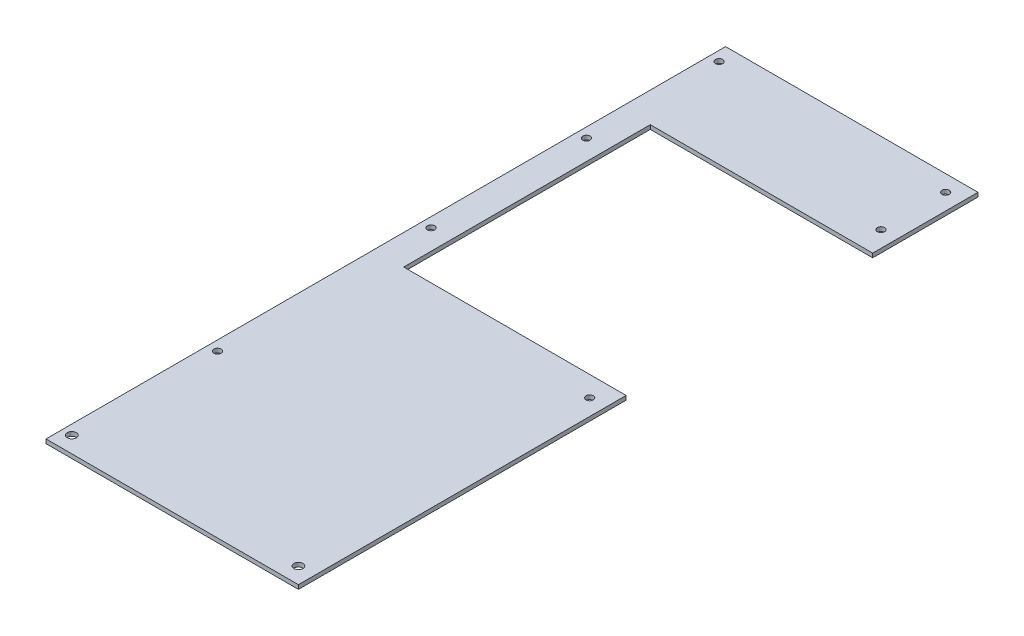
SolidWorks part; units mm, degrees
ref_plane "Front Plane" through (0, 0, 0) normal (1, 0, 0) x (0, 1, 0)
ref_plane "Top Plane" through (0, 0, 0) normal (0, 0, 1) x (0, 1, 0)
ref_plane "Right Plane" through (0, 0, 0) normal (0, 1, 0) x (-1, 0, 0)
sketch "Sketch1" plane through (0, 0, 0) normal (0, 1, 0) x (-1, 0, 0)
  line L0 (187.5, 235) -> (187.5, 275) construction
  line L1 (0, 275) -> (200, 275)
  line L2 (0, 275) -> (0, 525)
  line L3 (0, 525) -> (200, 525)
  line L4 (200, 275) -> (200, 525)
  line L5 (0, 275) -> (200, 525) construction
  line L6 (0, 525) -> (200, 275) construction
  line L7 (200, 275) -> (175, 275)
  line L8 (200, 275) -> (200, 0)
  line L9 (200, 0) -> (175, 0)
  line L10 (175, 275) -> (175, 0)
  line L11 (200, 275) -> (175, 0) construction
  line L12 (200, 0) -> (175, 275) construction
  line L13 (175, 0) -> (0, 0)
  line L14 (175, 0) -> (175, 75)
  line L15 (175, 75) -> (0, 75)
  line L16 (0, 0) -> (0, 75)
  line L17 (175, 0) -> (0, 75) construction
  line L18 (175, 75) -> (0, 0) construction
  line L19 (187.5, 115) -> (187.5, 0) construction
  line L20 (187.5, 512.5) -> (187.5, 235) construction
  circle A0 centre (12.5, 512.5) radius 3.5
  circle A1 centre (12.5, 287.5) radius 2.8
  circle A2 centre (187.5, 512.5) radius 3.5
  circle A3 centre (12.5, 62.5) radius 2.8
  circle A4 centre (12.5, 12.5) radius 2.8
  circle A5 centre (187.5, 12.5) radius 2.8
  circle A7 centre (187.5, 235) radius 2.8
  circle A8 centre (187.5, 115) radius 2.8
  circle A9 centre (187.5, 400) radius 2.8
  point P4 (100, 400)
  point P8 (187.5, 137.5)
  point P12 (87.5, 37.5)
  point P14 (0, 37.5)
  dimension "D7" = 5.6
  dimension "D22" = 7
  dimension "D1" = 25
  dimension "D2" = 250
  dimension "D3" = 200
  dimension "D4" = 200
  dimension "D5" = 200
  dimension "D6" = 75
  dimension "D8" = 12.5
  dimension "D9" = 12.5
  dimension "D10" = 12.5
  dimension "D11" = 12.5
  dimension "D12" = 12.5
  dimension "D13" = 12.5
  dimension "D14" = 12.5
  dimension "D15" = 12.5
  dimension "D16" = 12.5
  dimension "D17" = 12.5
  dimension "D18" = 12.5
  dimension "D19" = 12.5
  dimension "D20" = 40
  dimension "D21" = 40
  dimension "D23" = 125
extrude "Boss-Extrude1" add sketch "Sketch1" along normal blind 3.175 contours L1 L4 L3 L2 A2 A1 A0 | L1 L10 L9 L8 A8 A7 A5 | L16 L13 L10 L15 A4 A3 region at (-100, 0, 399.8819) region at (-187.5, 0, 137.6811) region at (-87.7825, 0, 37.5)
sketch "Sketch2" plane through (0, 3.175, 0) normal (0, 1, 0) x (-1, 0, 0)
  line L0 (175, 275) -> (175, 75) construction
  line L1 (0, 275) -> (175, 275)
  line L2 (0, 275) -> (0, 271.825)
  line L3 (0, 271.825) -> (175, 271.825)
  line L4 (175, 275) -> (175, 271.825)
  line L5 (0, 275) -> (175, 271.825) construction
  line L6 (0, 271.825) -> (175, 275) construction
  line L7 (175, 75) -> (0, 75) construction
  line L8 (175, 271.825) -> (171.825, 271.825)
  line L9 (175, 271.825) -> (175, 75)
  line L10 (175, 75) -> (171.825, 75)
  line L11 (171.825, 271.825) -> (171.825, 75)
  line L12 (175, 271.825) -> (171.825, 75) construction
  line L13 (175, 75) -> (171.825, 271.825) construction
  line L15 (0, 75) -> (171.825, 75)
  line L16 (0, 75) -> (0, 81.35)
  line L17 (0, 81.35) -> (171.825, 81.35)
  line L18 (171.825, 75) -> (171.825, 81.35)
  line L19 (0, 75) -> (171.825, 81.35) construction
  line L20 (0, 81.35) -> (171.825, 75) construction
  point P4 (87.5, 273.4125)
  point P11 (173.4125, 173.4125)
  point P17 (85.9125, 78.175)
  line M9 (0, 275) -> (175, 275)
  line M10 (175, 275) -> (175, 75)
  line M11 (175, 75) -> (0, 75)
  dimension "D1" = 3.175
  dimension "D2" = 3.175
  dimension "D3" = 6.35
extrude "Boss-Extrude2" add sketch "Sketch2" against normal through all contours L2 L3 M10 M9 | L3 L11 M11 M10 | L17 L16 L11 M11 region at (-87.5, 3.175, 273.4125) region at (-173.4125, 3.175, 173.4125) region at (-85.9125, 3.175, 78.175)
sketch "Sketch3" plane through (0, 3.175, 0) normal (0, 1, 0) x (-1, 0, 0)
  line L0 (200, 0) -> (0, 0) construction
  line L1 (200, 525) -> (195, 525)
  line L2 (200, 525) -> (200, 0)
  line L3 (200, 0) -> (195, 0)
  line L4 (195, 525) -> (195, 0)
  line L5 (200, 525) -> (195, 0) construction
  line L6 (200, 0) -> (195, 525) construction
  point P4 (197.5, 262.5)
  dimension "D1" = 5
extrude "Cut-Extrude1" cut sketch "Sketch3" against normal through all
